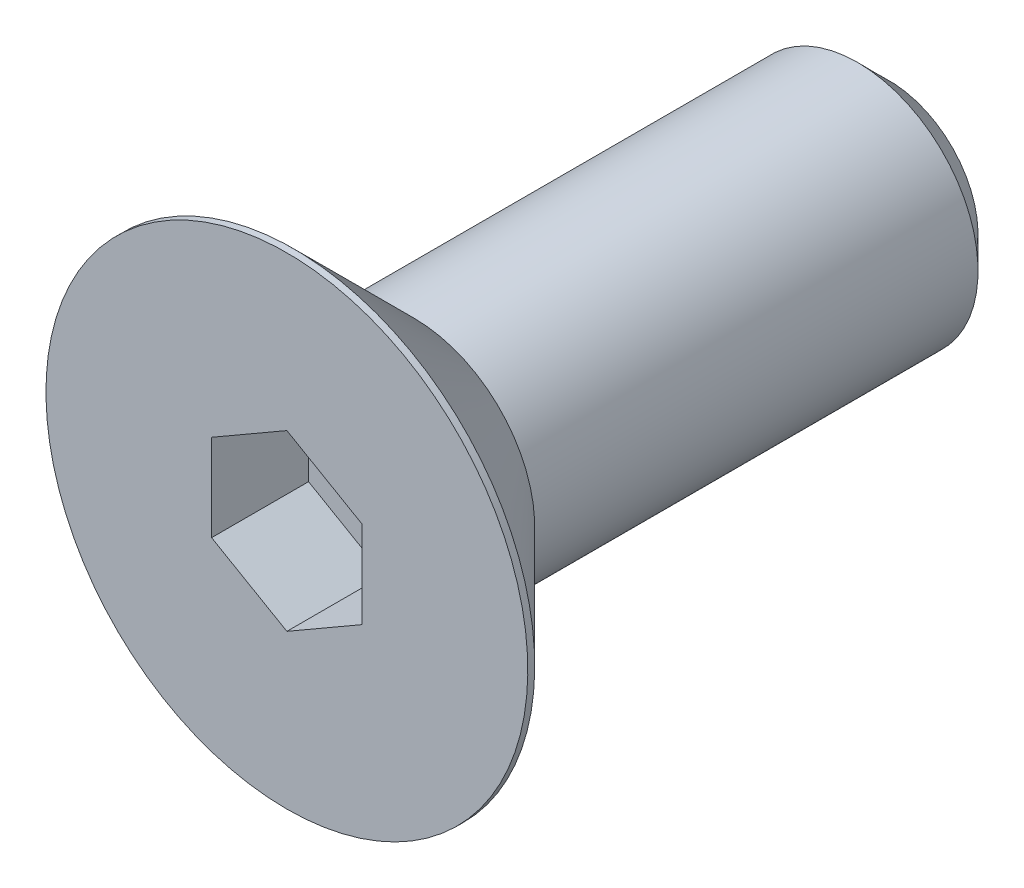
SolidWorks part; units mm, degrees
ref_plane "Front" through (0, 0, 0) normal (0, 0, 1) x (1, 0, 0)
ref_plane "Top" through (0, 0, 0) normal (0, 1, 0) x (1, 0, 0)
ref_plane "Right" through (0, 0, 0) normal (1, 0, 0) x (0, 0, -1)
sketch "Sketch11" plane through (0, 0, 0) normal (1, 0, 0) x (0, 0, -1)
  line L0 (-5, 4) -> (5, 4) construction
  line L5 (-5, 4) -> (-5, -4) construction
  line L6 (5, 2) -> (5, -2) construction
  line L7 (-4.99, 1.25) -> (-4.99, -1.25) construction
  line L8 (4.9562, 2.0758) -> (5.6563, 2.0758) construction
  line L9 (5.6563, 2.0758) -> (5.3062, 1.4696) construction
  line L10 (5.3062, 1.4696) -> (4.9562, 2.0758) construction
  line L11 (5.2625, 1.5453) -> (5.35, 1.5453) construction
  line L12 (5.3062, 1.5453) -> (5.3062, 1.4696) construction
  line L13 (4.9781, 2.0379) -> (5.6344, 2.0379) construction
  line L14 (5.3062, 2.0758) -> (5.3062, 2) construction
  line L15 (5, 2) -> (5.6125, 2) construction
  line L17 (-4.885, 4) -> (-0.885, 0) construction
  line L18 (-0.885, 0) -> (-4.885, -4) construction
  point P3 (-2.7, 4)
  point P8 (0, 4)
  point P21 (5.3062, 2.0379)
  point P26 (-5, 0)
  point P28 (-4.99, 0)
  point P29 (5, 0)
  dimension "Length" = 10
  dimension "Head Diameter" = 8
  dimension "Thread Major Diameter" = 4
  dimension "Head Height" = 2.3
  dimension "Drive Size" = 2.5
  dimension "Thread Pitch" = 0.7
  dimension "D1" = 0.0875
  dimension "D2" = 0.01
  dimension "D3" = 0.115
  dimension "Countersink Angle" = 90
sketch "Sketch1" plane through (0, 0, 0) normal (1, 0, 0) x (0, 0, -1)
  line L2 (-2.7, 2) -> (5, 2)
  line L3 (5, 2) -> (5, 0)
  line L4 (-3.39, 2) -> (-3.39, 0)
  line L5 (-2.7, 2) -> (-3.39, 2)
  line L6 (-5, 4) -> (-5, -4) construction
  line L7 (5, 2) -> (5, -2) construction
  line L8 (-3.39, 0) -> (5, 0)
  dimension "D1" = 1.61
revolve "Revolve1" add sketch "Sketch1" angle 360 mid plane about L8
chamfer "Chamfer1" distance 0.525 angle 45 1 edges at (0, -2, -5)
sketch "Sketch7" plane through (0, 0, 0) normal (1, 0, 0) x (0, 0, -1)
  line L2 (-5, 4) -> (-4.885, 4)
  line L5 (-2.7, 1.815) -> (-2.7, 0)
  line L6 (-5, 4) -> (-5, 0)
  line L8 (-5, 4) -> (-5, -4) construction
  line L9 (-5, 0) -> (-2.7, 0)
  line L12 (-4.885, 4) -> (-2.7, 1.815)
  line L13 (-4.885, 4) -> (-0.885, 0) construction
revolve "Revolve2" add sketch "Sketch7" angle 360 mid plane about L9 region at (0, 1.5544, 3.9977)
ref_plane "Plane1" through (0, 0, 2.7) normal (0, 0, 1) x (1, 0, 0)
sketch "Sketch5" plane through (0, 0, 5) normal (0, 0, 1) x (1, 0, 0)
  line L1 (1.25, -0.7217) -> (1.25, 0.7217)
  line L2 (1.25, 0.7217) -> (0, 1.4434)
  line L3 (0, 1.4434) -> (-1.25, 0.7217)
  line L4 (-1.25, 0.7217) -> (-1.25, -0.7217)
  line L5 (-1.25, -0.7217) -> (0, -1.4434)
  line L6 (0, -1.4434) -> (1.25, -0.7217)
  circle A0 centre (0, 0) radius 1.25 construction
extrude "Cut-Extrude2" cut sketch "Sketch5" against normal blind 1.61
sketch "Sketch6" plane through (0, 0, 5) normal (0, 0, -1) x (-1, 0, 0)
  circle A0 centre (0, 0) radius 1.4434
extrude "Cut-Extrude3" [suppressed] cut sketch "Sketch6" along normal blind 1.61 draft 45
sketch "Sketch12" [suppressed] plane through (0, 0, -5) normal (0, 0, -1) x (-1, 0, 0)
  circle A0 centre (0, 0) radius 2 construction
  circle A1 centre (0, 0) radius 2
curve "Helix/Spiral1" [suppressed] pitch 0.7 height 10 turns 14.2857
sketch "Sketch13" [suppressed] plane through (0, 0, 0) normal (1, 0, 0) x (0, 0, -1)
  line L0 (4.9781, 2.0379) -> (5.6344, 2.0379)
  line L1 (5.6344, 2.0379) -> (5.35, 1.5453)
  line L2 (5.35, 1.5453) -> (5.2625, 1.5453)
  line L3 (5.2625, 1.5453) -> (4.9781, 2.0379)
sweep "Cut-Sweep1" [suppressed] cut profiles "Sketch13" path "Helix/Spiral1"
combine bodies "Combine1" [suppressed] operation type add bodies to combine 113 127
equation "\"D1@Chamfer1\"=\"Thread Pitch@Sketch11\" * .75"
equation "\"D1@Cut-Extrude2\"= \"Head Height@Sketch11\" * .7"
equation "\"D1@Cut-Extrude3\" = \"D1@Cut-Extrude2\""
equation "\"D1@Sketch11\"=\"Thread Pitch@Sketch11\"/8"
equation "\"D3@Sketch11\"=\"Head Height@Sketch11\"*.05"
equation "\"D4@Helix/Spiral1\"=\"Thread Pitch@Sketch11\""
equation "\"D1@Sketch1\"=\"Head Height@Sketch11\"*.7"
equation "\"D3@Helix/Spiral1\"=\"Length@Sketch11\""
